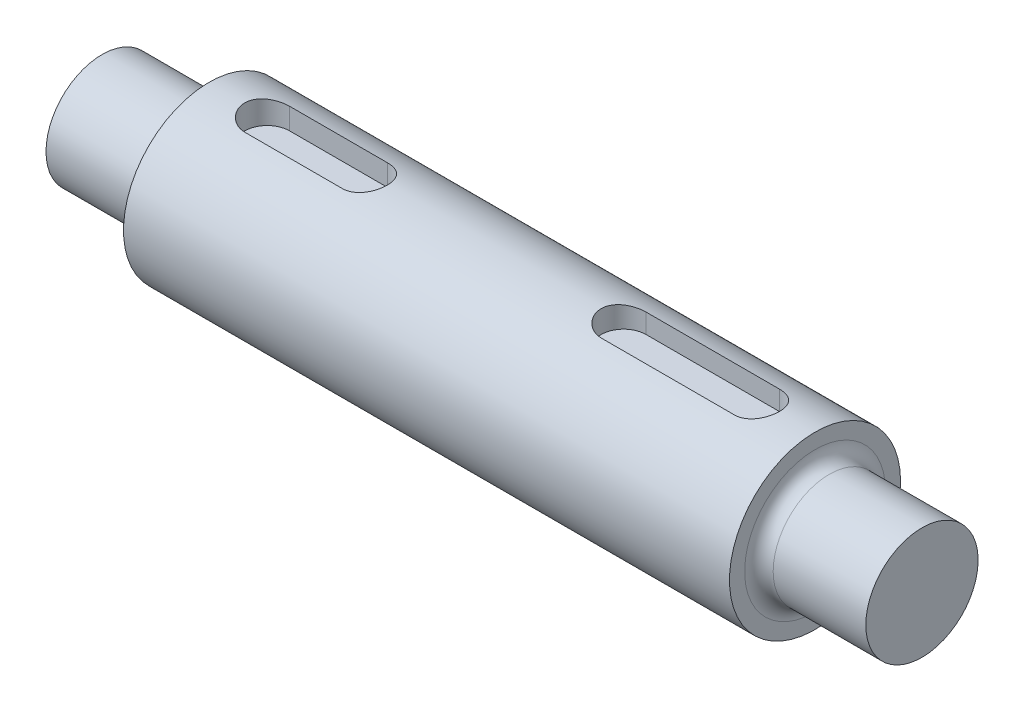
SolidWorks part; units mm, degrees
ref_plane "Front" through (0, 0, 0) normal (0, 0, 1) x (1, 0, 0)
ref_plane "Top" through (0, 0, 0) normal (0, 1, 0) x (1, 0, 0)
ref_plane "Right" through (0, 0, 0) normal (1, 0, 0) x (0, 0, -1)
sketch "Sketch1" plane through (0, 0, 0) normal (1, 0, 0) x (0, 0, -1)
  circle A0 centre (0, 0) radius 20
  dimension "D1" = 40
extrude "Boss-Extrude1" add sketch "Sketch1" along normal blind 38.1
sketch "Sketch2" plane through (38.1, 0, 0) normal (1, 0, 0) x (0, 0, -1)
  circle A0 centre (0, 0) radius 30.48
  dimension "D1" = 60.96
extrude "Boss-Extrude2" add sketch "Sketch2" along normal blind 215.9
sketch "Sketch3" plane through (254, 0, 0) normal (1, 0, 0) x (0, 0, -1)
  circle A0 centre (0, 0) radius 20
  dimension "D1" = 40
extrude "Boss-Extrude3" add sketch "Sketch3" along normal blind 38.1
fillet "Fillet1" radius 5.08 2 edges at (254, 0, -20) (38.1, 0, -20)
ref_plane "Plane1" through (50.8, 0, 0) normal (-1, 0, 0) x (0, 0, 1)
sketch "Sketch6" plane through (50.8, 0, 0) normal (1, 0, 0) x (0, 0, -1)
  line L1 (8.001, 21.812) -> (-8.001, 21.812)
  line L2 (8.001, 21.812) -> (8.001, 37.814)
  line L3 (8.001, 37.814) -> (-8.001, 37.814)
  line L4 (-8.001, 21.812) -> (-8.001, 37.814)
  line L5 (8.001, 21.812) -> (-8.001, 37.814) construction
  line L6 (8.001, 37.814) -> (-8.001, 21.812) construction
  point P0 (0, 29.813)
  dimension "D1" = 16.002
  dimension "D2" = 16.002
  dimension "D3" = 29.813
  dimension "D4" = 0
extrude "Cut-Extrude1" cut sketch "Sketch6" along normal blind 50.8
ref_plane "Plane2" through (177.8, 0, 0) normal (-1, 0, 0) x (0, 0, 1)
sketch "Sketch7" plane through (177.8, 0, 0) normal (-1, 0, 0) x (0, 0, 1)
  line L1 (-8, 38.48) -> (8, 38.48)
  line L2 (-8, 38.48) -> (-8, 22.48)
  line L3 (-8, 22.48) -> (8, 22.48)
  line L4 (8, 38.48) -> (8, 22.48)
  line L5 (-8, 38.48) -> (8, 22.48) construction
  line L6 (-8, 22.48) -> (8, 38.48) construction
  point P0 (0, 30.48)
  dimension "D1" = 16
  dimension "D2" = 16
  dimension "D3" = 30.48
extrude "Cut-Extrude2" cut sketch "Sketch7" against normal blind 63.5
sketch "Sketch8" plane through (0, 21.812, 0) normal (0, 1, 0) x (1, 0, 0)
  line L0 (101.6, 0) -> (101.6, 8.001) construction
  line L1 (101.6, 8.001) -> (93.599, 8.001) construction
  line L2 (93.599, -8.001) -> (101.6, -8.001) construction
  line L3 (50.8, -8.001) -> (58.801, -8.001) construction
  line L4 (50.8, 8.001) -> (50.8, -8.001)
  line L5 (50.8, -8.001) -> (101.6, -8.001)
  line L6 (101.6, -8.001) -> (101.6, 8.001)
  line L7 (101.6, 8.001) -> (50.8, 8.001)
  line L8 (50.8, 8.001) -> (50.8, 0) construction
  line L9 (58.801, -8.001) -> (93.599, -8.001)
  line L10 (101.6, -8.001) -> (101.6, 0) construction
  line L11 (93.599, 8.001) -> (58.801, 8.001)
  line L12 (50.8, 0) -> (50.8, -8.001) construction
  line L13 (58.801, 8.001) -> (50.8, 8.001) construction
  arc A0 (58.801, 8.001) -> (58.801, -8.001) centre (58.801, 0) ccw
  arc A1 (93.599, -8.001) -> (93.599, 8.001) centre (93.599, 0) ccw
  arc A2 (58.801, -8.001) -> (58.801, 8.001) centre (58.801, 0) ccw construction
  arc A3 (93.599, 8.001) -> (93.599, -8.001) centre (93.599, 0) ccw construction
  line M7 (50.8, 8.001) -> (50.8, -8.001)
  line M8 (50.8, -8.001) -> (101.6, -8.001)
  line M9 (101.6, -8.001) -> (101.6, 8.001)
  line M10 (101.6, 8.001) -> (50.8, 8.001)
  dimension "D1" = 0
extrude "Boss-Extrude4" add sketch "Sketch8" along normal up to surface (7.5991 mm away) contours A0 M10 M7 | A0 M7 M8 | A1 M8 M9 | A1 M9 M10 region at (52.5872, 21.812, -6.2138) region at (52.5872, 21.812, 6.2138) region at (99.8128, 21.812, -6.2138) region at (99.8128, 21.812, 6.2138) up to face at (38.1, 0, -30.48)
sketch "Sketch10" plane through (0, 22.48, 0) normal (0, 1, 0) x (1, 0, 0)
  line L0 (185.8, 8) -> (177.8, 8)
  line L1 (177.8, 22) -> (177.8, -22) construction
  line L2 (177.8, 8) -> (241.3, 8) construction
  line L3 (177.8, 8) -> (177.8, -8)
  line L4 (177.8, -8) -> (185.8, -8)
  line L5 (233.3, 8) -> (241.3, 8)
  line L6 (241.3, 8) -> (241.3, -8)
  line L7 (241.3, -8) -> (233.3, -8)
  line L10 (185.8, 8) -> (233.3, 8)
  line L11 (233.3, -8) -> (185.8, -8)
  line L12 (185.8, -8) -> (233.3, -8)
  arc A0 (185.8, 8) -> (185.8, -8) centre (185.8, 0) ccw
  arc A1 (233.3, -8) -> (233.3, 8) centre (233.3, 0) ccw
  line M7 (177.8, 8) -> (177.8, -8)
  line M8 (177.8, -8) -> (241.3, -8)
  line M9 (241.3, -8) -> (241.3, 8)
  line M10 (241.3, 8) -> (177.8, 8)
extrude "Boss-Extrude5" add sketch "Sketch10" along normal up to surface (6.9314 mm away) contours A0 M10 M7 | A0 L3 M8 | A1 M8 M9 | A1 L6 M10 region at (179.5869, 22.48, -6.2131) region at (239.5131, 22.48, -6.2131) region at (179.5869, 22.48, 6.2131) region at (239.5131, 22.48, 6.2131) up to face at (76.2, 29.9456, 0)
